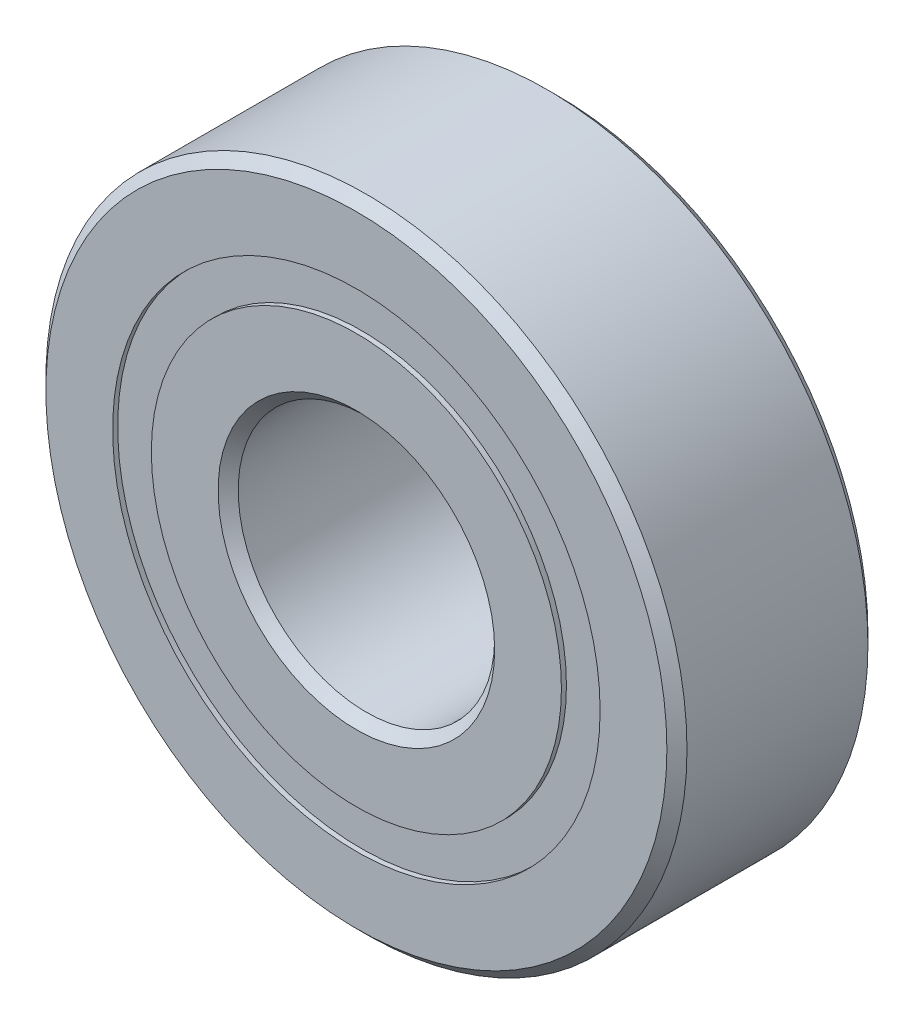
SolidWorks part; units mm, degrees
ref_plane "Front Plane" through (0, 0, 0) normal (0, 0, 1) x (1, 0, 0)
ref_plane "Top Plane" through (0, 0, 0) normal (0, 1, 0) x (1, 0, 0)
ref_plane "Right Plane" through (0, 0, 0) normal (1, 0, 0) x (0, 0, -1)
sketch "Sketch1" plane through (0, 0, 0) normal (1, 0, 0) x (0, 0, -1)
  line L0 (-2.4892, 0) -> (2.4892, 0) construction
  line L1 (0, 7.9375) -> (0, -7.9375) construction
  line L2 (2.2403, 7.9375) -> (-2.2403, 7.9375)
  line L3 (-2.2403, 7.9375) -> (-2.4892, 7.6886)
  line L4 (-2.4892, 7.6886) -> (-2.4892, 6.0352)
  line L5 (-2.4892, 6.0352) -> (-1.1063, 6.0352)
  line L6 (2.4892, 6.0352) -> (1.1063, 6.0352)
  line L7 (2.4892, 7.6886) -> (2.4892, 6.0352)
  line L8 (2.2403, 7.9375) -> (2.4892, 7.6886)
  line L9 (0, 7.9375) -> (0, 5.5563) construction
  line L10 (0, 5.5563) -> (0, 3.175) construction
  arc A0 (-1.1063, 6.0352) -> (1.1063, 6.0352) centre (0, 5.5563) cw
  point P14 (0, 3.175)
  dimension "Width" = 4.9784
  dimension "OD" = 15.875
  dimension "D1" = 45
  dimension "D2" = 0.2489
  dimension "Shaft Dia" = 6.35
  dimension "D3" = 2.2126
  dimension "D4" = 0.479
revolve "Revolve1" add sketch "Sketch1" angle 360 about L0
sketch "Sketch3" plane through (0, 0, 0) normal (1, 0, 0) x (0, 0, -1)
  line L0 (-2.4892, 5.0773) -> (-1.1063, 5.0773)
  line L1 (0, 7.9375) -> (0, -7.9375) construction
  line L2 (-2.4892, 7.6886) -> (-2.4892, 6.0352) construction
  line L3 (-2.4892, 5.0773) -> (-2.4892, 3.4239)
  line L4 (-2.2403, 7.9375) -> (-2.4892, 7.6886) construction
  line L5 (-2.4892, 3.4239) -> (-2.2403, 3.175)
  line L6 (-2.2403, 3.175) -> (2.2403, 3.175)
  line L7 (2.2403, 7.9375) -> (2.2403, -7.9375) construction
  line L8 (2.2403, 3.175) -> (2.4892, 3.4239)
  line L9 (2.4892, -7.6886) -> (2.4892, 7.6886) construction
  line L10 (2.4892, 3.4239) -> (2.4892, 5.0773)
  line L11 (2.4892, 5.0773) -> (1.1063, 5.0773)
  line L13 (2.2403, 7.9375) -> (2.4892, 7.6886) construction
  arc A0 (1.1063, 6.0352) -> (-1.1063, 6.0352) centre (0, 5.5563) ccw construction
  arc A1 (1.1063, 5.0773) -> (-1.1063, 5.0773) centre (0, 5.5562) cw
revolve "Revolve3" add sketch "Sketch3" angle 360 about L0
sketch "Sketch4" plane through (0, 0, 0) normal (1, 0, 0) x (0, 0, -1)
  line L0 (-1.2055, 5.5563) -> (1.2055, 5.5563)
  arc A2 (-1.2055, 5.5563) -> (1.2055, 5.5563) centre (0, 5.5563) cw
  arc A3 (1.1063, 6.0352) -> (-1.1063, 6.0352) centre (0, 5.5563) ccw construction
revolve "Revolve4" add sketch "Sketch4" angle 360 about L0
ref_axis "Axis1" through (0, 0, -2.4892) along (0, 0, 1)
pattern_circular "CirPattern1" count 8 every 45 about axis through (0, 0, -2.4892) along (0, 0, 1) of bodies 104
sketch "Sketch5" plane through (0, 0, 0) normal (1, 0, 0) x (0, 0, -1)
  line L0 (-2.4892, 6.0352) -> (-1.1063, 6.0352) construction
  line L1 (-2.3647, 6.0352) -> (-1.2055, 6.0352)
  line L2 (-2.3647, 6.0352) -> (-2.3647, 5.0773)
  line L3 (-2.3647, 5.0773) -> (-1.2055, 5.0773)
  line L4 (-1.2055, 6.0352) -> (-1.2055, 5.0773)
  line L5 (-2.4892, 5.0773) -> (-1.1063, 5.0773) construction
  line L6 (2.4892, 6.0352) -> (1.1063, 6.0352) construction
  line L7 (2.3647, 6.0352) -> (1.2055, 6.0352)
  line L8 (2.3647, 6.0352) -> (2.3647, 5.0773)
  line L9 (2.3647, 5.0773) -> (1.2055, 5.0773)
  line L10 (1.2055, 6.0352) -> (1.2055, 5.0773)
  line L11 (2.4892, 5.0773) -> (1.1063, 5.0773) construction
  line L12 (-2.2403, 7.9375) -> (-2.4892, 7.6886) construction
  point P18 (-2.3647, 7.813)
revolve "Revolve5" add sketch "Sketch5" angle 360 about L0
equation "\"D2@Sketch1\" = \"Width@Sketch1\"*.05"
equation "\"D3@Sketch1\" = \"Width@Sketch1\"/2.25"
equation "\"D4@Sketch1\" = (((\"OD@Sketch1\"-\"Width@Sketch1\")/2)/3.25)/3.5"
equation "\"D2@CirPattern1\" = 360/\"Balls@CirPattern1\""
